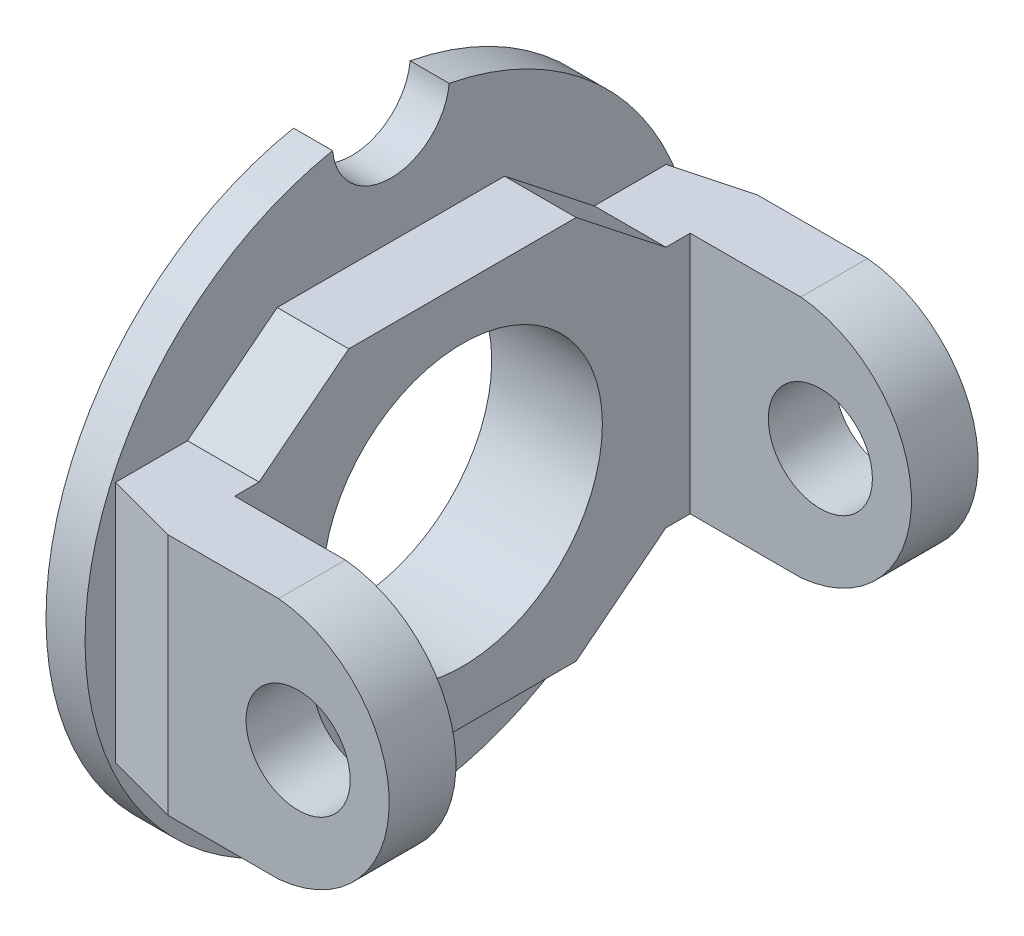
SolidWorks part; units mm, degrees
ref_plane "Front Plane" through (0, 0, 0) normal (0, 0, 1) x (1, 0, 0)
ref_plane "Top Plane" through (0, 0, 0) normal (0, 1, 0) x (1, 0, 0)
ref_plane "Right Plane" through (0, 0, 0) normal (1, 0, 0) x (0, 0, -1)
sketch "Sketch1" plane through (0, 0, 0) normal (1, 0, 0) x (0, 0, -1)
  line L0 (0, 0) -> (0, 19) construction
  circle A0 centre (0, 0) radius 10.75
  arc A1 (-4.4793, 23.0691) -> (4.4793, 23.0691) centre (0, 0) ccw
  arc A2 (-4.4793, 23.0691) -> (4.4793, 23.0691) centre (0, 23.5) ccw
  dimension "D1" = 21.5
  dimension "D2" = 47
  dimension "D3" = 4.5
  dimension "D4" = 23.5
extrude "Boss-Extrude1" add sketch "Sketch1" along normal blind 3
sketch "Sketch2" plane through (3, 0, 0) normal (1, 0, 0) x (0, 0, -1)
  line L0 (-15.6269, 9.3372) -> (-8.7368, 14.7601)
  line L1 (-8.7368, 14.7601) -> (8.7368, 14.7601)
  line L2 (8.7368, 14.7601) -> (15.6269, 9.3372)
  line L3 (15.6269, 9.3372) -> (15.6269, -9.3372)
  line L4 (15.6269, -9.3372) -> (8.7368, -14.7601)
  line L5 (8.7368, -14.7601) -> (-8.7368, -14.7601)
  line L6 (-8.7368, -14.7601) -> (-15.6269, -9.3372)
  line L7 (-15.6269, -9.3372) -> (-15.6269, 9.3372)
  line L8 (0, 14.7601) -> (0, -14.7601) construction
  line L9 (-15.6269, 0) -> (15.6269, 0) construction
  line L10 (15.6269, 9.3372) -> (22.6269, 9.3372)
  line L11 (22.6269, 9.3372) -> (22.6269, -9.3372)
  line L12 (22.6269, -9.3372) -> (15.6269, -9.3372)
  line L13 (-22.6269, -9.3372) -> (-15.6269, -9.3372)
  line L14 (-22.6269, 9.3372) -> (-22.6269, -9.3372)
  line L15 (-15.6269, 9.3372) -> (-22.6269, 9.3372)
  circle A0 centre (0, 0) radius 10.75 construction
  circle A1 centre (0, 0) radius 10.75
  arc M8 (-4.4793, 23.0691) -> (4.4793, 23.0691) centre (0, 0) ccw
  circle M9 centre (0, 0) radius 10.75
  dimension "D1" = 7
  dimension "D2" = 18.6744
  dimension "D3" = 8.7682
  dimension "D4" = 17.4736
extrude "Boss-Extrude2" add sketch "Sketch2" along normal blind 5.5 contours L15 L14 M8 | L14 L13 M8 | L11 L10 M8 | L12 L11 M8 | L12 L11 L10 L3 M8 | L7 L15 L14 L13 M8 | L7 L6 L5 L4 L3 L2 L1 L0 M9 region at (3, 11.7108, 11.916) region at (3, 0, 19.054) region at (3, 8.378, 22.2851) region at (3, -8.378, 22.2851) region at (3, 0, -19.054) region at (3, -8.378, -22.2851) region at (3, 8.378, -22.2851)
draft "Draft1" type of draft neutral plane draft angle 15 faces to draft 2 face at (4.8333, 0, -22.6269) face at (4.8333, 0, 22.6269) neutral plane through (8.5, 0, 0) neutral plane normal (1, 0, 0) reverse direction yes parameters "D1"=15
sketch "Sketch3" plane through (8.5, 0, 0) normal (1, 0, 0) x (0, 0, -1)
  line L0 (-21.1532, -9.3372) -> (-15.6269, -9.3372) construction
  line L1 (-22.6269, 9.3372) -> (-17.5, 9.3372)
  line L2 (-22.6269, 9.3372) -> (-22.6269, -9.3372)
  line L3 (-22.6269, -9.3372) -> (-17.5, -9.3372)
  line L4 (-17.5, 9.3372) -> (-17.5, -9.3372)
  line L5 (21.1532, -9.3372) -> (15.6269, -9.3372) construction
  line L6 (22.6269, 9.3372) -> (17.5, 9.3372)
  line L7 (22.6269, 9.3372) -> (22.6269, -9.3372)
  line L8 (22.6269, -9.3372) -> (17.5, -9.3372)
  line L9 (17.5, 9.3372) -> (17.5, -9.3372)
  dimension "D1" = 35
  dimension "D2" = 17.5
extrude "Boss-Extrude3" add sketch "Sketch3" along normal blind 17
sketch "Sketch4" plane through (0, 0, 22.6269) normal (0, 0, 1) x (1, 0, 0)
  line L0 (25.5, 9.3372) -> (25.5, -9.3372) construction
  line L1 (16.1216, 9.3784) -> (16.1216, -9.3784) construction
  line L2 (16.1216, 9.3784) -> (16.1216, 12.9184)
  line L3 (16.1216, 12.9184) -> (28.5616, 12.9184)
  line L4 (28.5616, 12.9184) -> (28.5616, -13.0516)
  line L5 (28.5616, -13.0516) -> (16.1216, -13.0516)
  line L6 (16.1216, -13.0516) -> (16.1216, -9.3784)
  arc A0 (16.1216, -9.3784) -> (16.1216, 9.3784) centre (16.1216, 0) ccw
  dimension "D1" = 9.3784
  dimension "D2" = 3.54
  dimension "D3" = 12.44
  dimension "D4" = 25.97
extrude "Cut-Extrude1" cut sketch "Sketch4" against normal blind 47
sketch "Sketch5" plane through (0, 0, 22.6269) normal (0, 0, 1) x (1, 0, 0)
  line L0 (25.5, 0) -> (18.5, 0) construction
  arc A2 (17, -9.3372) -> (17, 9.3372) centre (16.1216, 0) ccw construction
  circle A3 centre (18.5, 0) radius 4
  dimension "D1" = 8
  dimension "D2" = 7
extrude "Cut-Extrude2" cut sketch "Sketch5" against normal blind 47
